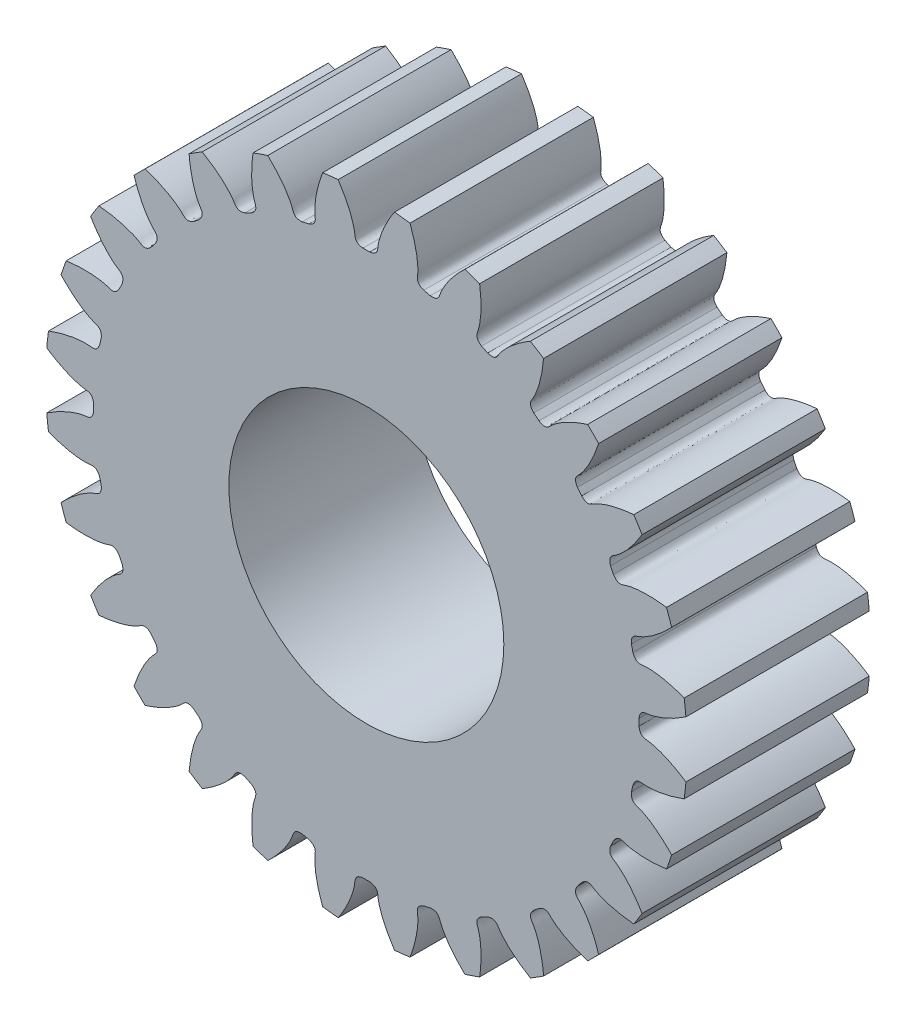
SolidWorks part; units mm, degrees
material "40Cr"
ref_plane "前视基准面" through (0, 0, 0) normal (0, 0, 1) x (1, 0, 0)
ref_plane "上视基准面" through (0, 0, 0) normal (0, 1, 0) x (1, 0, 0)
ref_plane "右视基准面" through (0, 0, 0) normal (1, 0, 0) x (0, 0, -1)
sketch "草图1" plane through (0, 0, 0) normal (0, 0, 1) x (1, 0, 0)
  circle A0 centre (0, 0) radius 10.5
ref_axis "基准轴1" through (0, 0, -11.55) along (0, 0, 1)
sketch "草图2" plane through (0, 0, 0) normal (0, 0, 1) x (1, 0, 0)
  line L0 (0, 0) -> (0, 10.5) construction
  circle A0 centre (0, 0) radius 10.5 construction
  arc A1 (0.1096, 8.9243) -> (-0.1096, 8.9243) centre (0, 0) ccw
  arc A2 (2.3053, 11.9253) -> (-2.3053, 11.9253) centre (0, 0) ccw
  spline S0 degree 3 poles (0.1096, 8.9243) (0.381, 8.9598) (0.3638, 9.1131) (0.3877, 9.2682) (0.3918, 9.2918) (0.397, 9.3189) (0.4036, 9.3495) (0.4117, 9.3836) (0.4213, 9.421) (0.4327, 9.4618) (0.4459, 9.5059) (0.4611, 9.5533) (0.4785, 9.6038) (0.4982, 9.6574) (0.5203, 9.714) (0.5449, 9.7736) (0.5721, 9.8361) (0.6022, 9.9013) (0.6351, 9.9693) (0.6711, 10.0398) (0.7102, 10.1129) (0.7526, 10.1884) (0.7983, 10.2662) (0.8475, 10.3462) (0.9003, 10.4283) (0.9568, 10.5124) (1.0171, 10.5984) (1.0812, 10.6861) (1.1493, 10.7755) (1.2215, 10.8663) (1.2978, 10.9586) (1.3784, 11.052) (1.4633, 11.1466) (1.5526, 11.2422) (1.6463, 11.3386) (1.7446, 11.4357) (1.8474, 11.5333) (1.9549, 11.6314) (2.1064, 11.7641) (2.2244, 11.8613) (2.3053, 11.9253) knots 0 0 0 0 0.112672 0.118023 0.124348 0.131645 0.139915 0.149158 0.159374 0.170563 0.182724 0.195859 0.209967 0.225048 0.241101 0.258128 0.276127 0.2951 0.315045 0.335964 0.357855 0.380719 0.404556 0.429367 0.45515 0.481906 0.509635 0.538337 0.568012 0.598659 0.63028 0.662874 0.696441 0.73098 0.766493 0.802978 0.840437 0.878868 0.918272 1 1 1 1
  spline S1 degree 3 poles (-0.1096, 8.9243) (-0.381, 8.9598) (-0.3638, 9.1131) (-0.3877, 9.2682) (-0.3918, 9.2918) (-0.397, 9.3189) (-0.4036, 9.3495) (-0.4117, 9.3836) (-0.4213, 9.421) (-0.4327, 9.4618) (-0.4459, 9.5059) (-0.4611, 9.5533) (-0.4785, 9.6038) (-0.4982, 9.6574) (-0.5203, 9.714) (-0.5449, 9.7736) (-0.5721, 9.8361) (-0.6022, 9.9013) (-0.6351, 9.9693) (-0.6711, 10.0398) (-0.7102, 10.1129) (-0.7526, 10.1884) (-0.7983, 10.2662) (-0.8475, 10.3462) (-0.9003, 10.4283) (-0.9568, 10.5124) (-1.0171, 10.5984) (-1.0812, 10.6861) (-1.1493, 10.7755) (-1.2215, 10.8663) (-1.2978, 10.9586) (-1.3784, 11.052) (-1.4633, 11.1466) (-1.5526, 11.2422) (-1.6463, 11.3386) (-1.7446, 11.4357) (-1.8474, 11.5333) (-1.9549, 11.6314) (-2.1064, 11.7641) (-2.2244, 11.8613) (-2.3053, 11.9253) knots 0 0 0 0 0.112672 0.118023 0.124348 0.131645 0.139915 0.149158 0.159374 0.170563 0.182724 0.195859 0.209967 0.225048 0.241101 0.258128 0.276127 0.2951 0.315045 0.335964 0.357855 0.380719 0.404556 0.429367 0.45515 0.481906 0.509635 0.538337 0.568012 0.598659 0.63028 0.662874 0.696441 0.73098 0.766493 0.802978 0.840437 0.878868 0.918272 1 1 1 1
extrude "凸台-拉伸1" add sketch "草图1" along normal blind 6
extrude "切除-拉伸1" cut sketch "草图2" along normal blind 6
pattern_circular "阵列(圆周)1" count 28 every 12.857 about axis through (0, 0, -11.55) along (0, 0, 1) of "切除-拉伸1"
sketch "草图3" plane through (0, 0, 0) normal (0, 0, 1) x (1, 0, 0)
  circle A0 centre (0, 0) radius 9.8 construction
  dimension "Dn" = 19.6
sketch "草图4" plane through (0, 0, 6) normal (0, 0, 1) x (1, 0, 0)
  circle A0 centre (0, 0) radius 4.5
  dimension "D1" = 9
extrude "切除-拉伸2" cut sketch "草图4" against normal through all
